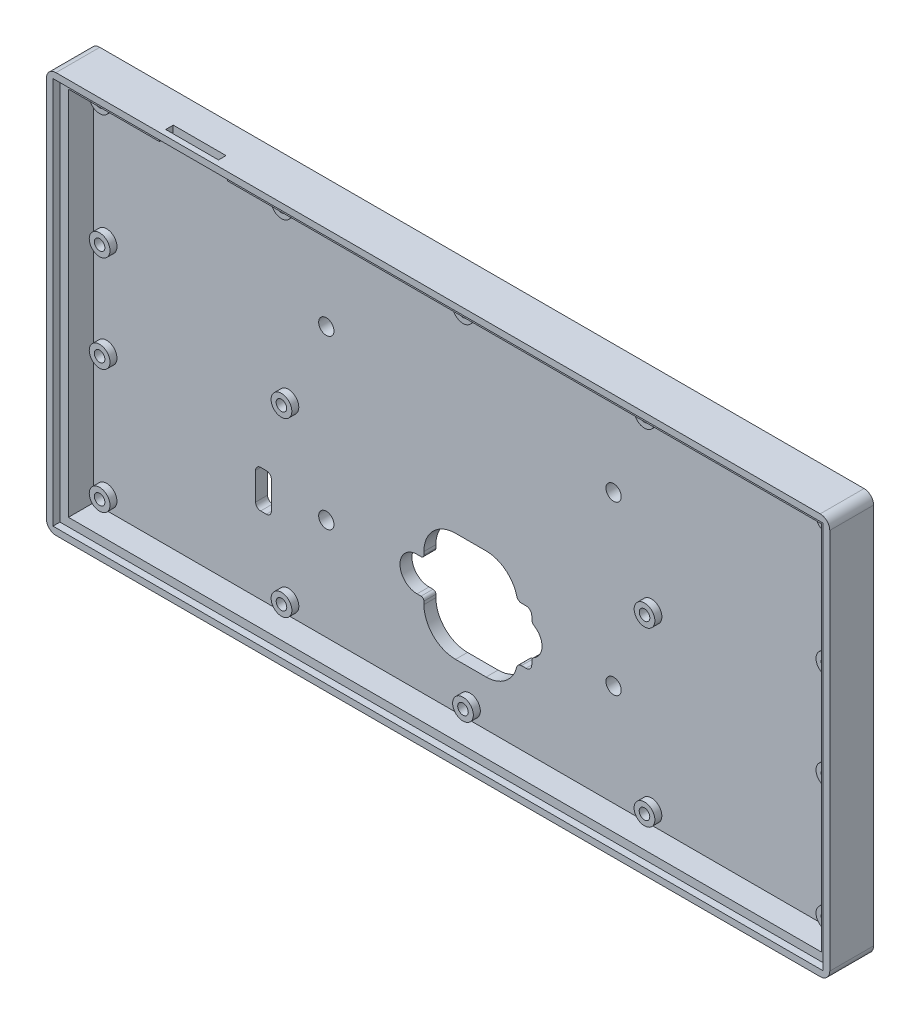
SolidWorks part; units mm, degrees
ref_plane "Front Plane" through (0, 0, 0) normal (0, 0, 1) x (1, 0, 0)
ref_plane "Top Plane" through (0, 0, 0) normal (0, 1, 0) x (1, 0, 0)
ref_plane "Right Plane" through (0, 0, 0) normal (1, 0, 0) x (0, 0, -1)
sketch "PCB" plane through (0, 0, 0) normal (0, 0, 1) x (1, 0, 0)
  line L0 (96.2635, 45.5524) -> (101.8921, 45.5524) construction
  line L1 (-101.8921, 51.181) -> (101.8921, 51.181) construction
  line L2 (-101.8921, 51.181) -> (-101.8921, -51.181) construction
  line L3 (-101.8921, -51.181) -> (101.8921, -51.181) construction
  line L4 (101.8921, 51.181) -> (101.8921, -51.181) construction
  line L5 (-101.8921, 51.181) -> (101.8921, -51.181) construction
  line L6 (-101.8921, -51.181) -> (101.8921, 51.181) construction
  line L7 (96.2635, 45.5524) -> (96.2635, 51.181) construction
  line L8 (-96.2635, 45.5524) -> (-101.8921, 45.5524) construction
  line L9 (-96.2635, -45.5524) -> (-96.2635, -51.181) construction
  line L10 (-92.8243, 0) -> (-92.8243, 25.6794) construction
  line L11 (-98.8568, 31.7119) -> (-86.7918, 31.7119)
  line L12 (-98.8568, 31.7119) -> (-98.8568, 19.6469)
  line L13 (-98.8568, 19.6469) -> (-86.7918, 19.6469)
  line L14 (-86.7918, 31.7119) -> (-86.7918, 19.6469)
  line L15 (-98.8568, 31.7119) -> (-86.7918, 19.6469) construction
  line L16 (-98.8568, 19.6469) -> (-86.7918, 31.7119) construction
  line L17 (-98.8568, 6.0325) -> (-86.7918, 6.0325)
  line L18 (-98.8568, 6.0325) -> (-98.8568, -6.0325)
  line L19 (-98.8568, -6.0325) -> (-86.7918, -6.0325)
  line L20 (-86.7918, 6.0325) -> (-86.7918, -6.0325)
  line L21 (-98.8568, 6.0325) -> (-86.7918, -6.0325) construction
  line L22 (-98.8568, -6.0325) -> (-86.7918, 6.0325) construction
  line L23 (-98.8568, -19.6469) -> (-86.7918, -19.6469)
  line L24 (-98.8568, -19.6469) -> (-98.8568, -31.7119)
  line L25 (-98.8568, -31.7119) -> (-86.7918, -31.7119)
  line L26 (-86.7918, -19.6469) -> (-86.7918, -31.7119)
  line L27 (-98.8568, -19.6469) -> (-86.7918, -31.7119) construction
  line L28 (-98.8568, -31.7119) -> (-86.7918, -19.6469) construction
  line L29 (86.7918, 31.7119) -> (98.8568, 31.7119)
  line L30 (86.7918, 31.7119) -> (86.7918, 19.6469)
  line L31 (86.7918, 19.6469) -> (98.8568, 19.6469)
  line L32 (98.8568, 31.7119) -> (98.8568, 19.6469)
  line L33 (86.7918, 31.7119) -> (98.8568, 19.6469) construction
  line L34 (86.7918, 19.6469) -> (98.8568, 31.7119) construction
  line L35 (86.7918, 6.0325) -> (98.8568, 6.0325)
  line L36 (86.7918, 6.0325) -> (86.7918, -6.0325)
  line L37 (86.7918, -6.0325) -> (98.8568, -6.0325)
  line L38 (98.8568, 6.0325) -> (98.8568, -6.0325)
  line L39 (86.7918, 6.0325) -> (98.8568, -6.0325) construction
  line L40 (86.7918, -6.0325) -> (98.8568, 6.0325) construction
  line L41 (86.7918, -19.6469) -> (98.8568, -19.6469)
  line L42 (86.7918, -19.6469) -> (86.7918, -31.7119)
  line L43 (86.7918, -31.7119) -> (98.8568, -31.7119)
  line L44 (98.8568, -19.6469) -> (98.8568, -31.7119)
  line L45 (86.7918, -19.6469) -> (98.8568, -31.7119) construction
  line L46 (86.7918, -31.7119) -> (98.8568, -19.6469) construction
  line L47 (-92.8243, 0) -> (-92.8243, -25.6794) construction
  line L48 (-92.8243, 25.6794) -> (-101.8921, 25.6794) construction
  line L49 (92.8243, 25.6794) -> (101.8921, 25.6794) construction
  line L50 (-3.114, -17.4711) -> (-3.114, -27.7327) construction
  circle A0 centre (-96.2635, 45.5524) radius 0.9995
  circle A1 centre (-96.2635, -45.5524) radius 0.9995
  circle A2 centre (96.2635, -45.5524) radius 0.9995
  circle A3 centre (96.2635, 45.5524) radius 0.9995
  circle A4 centre (-3.114, -17.4711) radius 1.9939
  circle A5 centre (-3.114, -27.7327) radius 1.9939
  point P0 (0, 0)
  point P14 (-92.8243, 25.6794)
  point P23 (-92.8243, 0)
  point P28 (-92.8243, -25.6794)
  point P33 (92.8243, 25.6794)
  point P38 (92.8243, 0)
  point P43 (92.8243, -25.6794)
  point P54 (0.1092, -22.6019)
  point P55 (-7.5006, -22.6019)
  point P60 (-3.114, -22.6019)
  dimension "D4" = 1.999
  dimension "D14" = 3.9878
  dimension "D1" = 203.7842
  dimension "D2" = 102.362
  dimension "D3" = 5.6286
  dimension "D5" = 25.5016
  dimension "D6" = 25.5016
  dimension "D7" = 9.0678
  dimension "D8" = 12.065
  dimension "D9" = 102.0013
  dimension "D10" = 28.5791
  dimension "D11" = 7.6098
  dimension "D12" = 5.1308
  dimension "D13" = 3.2233
sketch "DT_plug" plane through (0, 0, 0) normal (0, 0, 1) x (1, 0, 0)
  line L0 (29.2774, -40.0231) -> (29.2774, -5.0981) construction
  dimension "D1" = 34.925
sketch "display_screen" plane through (0, 0, 0) normal (0, 0, 1) x (1, 0, 0)
  line L1 (-80.3275, 46.3296) -> (83.7565, 46.3296) construction
  line L2 (-80.3275, 46.3296) -> (-80.3275, -50.9016) construction
  line L3 (-80.3275, -50.9016) -> (83.7565, -50.9016) construction
  line L4 (83.7565, 46.3296) -> (83.7565, -50.9016) construction
  line L5 (-78.2955, 44.2976) -> (78.2955, 44.2976) construction
  line L6 (-78.2955, 44.2976) -> (-78.2955, -44.2976) construction
  line L7 (-78.2955, -44.2976) -> (78.2955, -44.2976) construction
  line L8 (78.2955, 44.2976) -> (78.2955, -44.2976) construction
  point P8 (0, 44.2976)
  point P10 (-78.2955, 0)
  dimension "D1" = 164.084
  dimension "D2" = 97.2312
  dimension "D3" = 6.604
  dimension "D4" = 2.032
  dimension "D5" = 2.032
  dimension "D6" = 5.461
ref_plane "back_of_PCB" through (0, 0, -1.8542) normal (0, 0, 1) x (1, 0, 0)
ref_plane "back_PCB_clearance" through (0, 0, -8.4582) normal (0, 0, 1) x (1, 0, 0)
sketch "Sketch4" plane through (0, 0, 0) normal (0, 0, 1) x (1, 0, 0)
  line L0 (-102.1461, 51.4096) -> (-102.1461, 53.1596) construction
  line L1 (-102.1461, 51.4096) -> (102.1461, 51.4096)
  line L2 (-102.1461, 51.4096) -> (-102.1461, -51.4096)
  line L3 (-102.1461, -51.4096) -> (102.1461, -51.4096)
  line L4 (102.1461, 51.4096) -> (102.1461, -51.4096)
  line L5 (-103.8961, 53.1596) -> (103.8961, 53.1596)
  line L6 (-103.8961, 53.1596) -> (-103.8961, -53.1596)
  line L7 (-103.8961, -53.1596) -> (103.8961, -53.1596)
  line L8 (103.8961, 53.1596) -> (103.8961, -53.1596)
  line L9 (-102.1461, 51.4096) -> (-103.8961, 51.4096) construction
  line L10 (102.1461, -51.4096) -> (102.1461, -53.1596) construction
  line L11 (102.1461, -51.4096) -> (103.8961, -51.4096) construction
  line L12 (-101.8921, 51.181) -> (101.8921, 51.181) construction
  line L13 (-101.8921, 51.181) -> (-101.8921, -51.181) construction
  line L14 (101.8921, 51.181) -> (101.8921, -51.181) construction
  line L15 (-101.8921, -51.181) -> (101.8921, -51.181) construction
  dimension "D1" = 1.75
  dimension "D2" = 0.2286
  dimension "D3" = 0.254
  dimension "D4" = 0.254
  dimension "D5" = 0.2286
extrude "Boss-Extrude1" add sketch "Sketch4" against normal up to surface (1.8542 mm away) up to plane "back_of_PCB"
sketch "Sketch5" plane through (0, 0, -1.8542) normal (0, 0, -1) x (-1, 0, 0)
  line L1 (-103.8961, 53.1596) -> (103.8961, 53.1596)
  line L2 (-103.8961, 53.1596) -> (-103.8961, -53.1596)
  line L3 (-103.8961, -53.1596) -> (103.8961, -53.1596)
  line L4 (103.8961, 53.1596) -> (103.8961, -53.1596)
  line L6 (101.8921, 51.181) -> (-101.8921, 51.181) construction
  line L7 (-99.8931, 49.182) -> (99.8931, 49.182)
  line L8 (-99.8931, 49.182) -> (-99.8931, -49.182)
  line L9 (-99.8931, -49.182) -> (99.8931, -49.182)
  line L10 (99.8931, 49.182) -> (99.8931, -49.182)
  line L11 (-99.8931, 49.182) -> (-99.8931, 51.181) construction
  line L12 (-99.8931, 49.182) -> (-101.8921, 49.182) construction
  line L13 (-101.8921, 51.181) -> (-101.8921, -51.181) construction
  line L14 (99.8931, -49.182) -> (101.8921, -49.182) construction
  line L15 (101.8921, 51.181) -> (101.8921, -51.181) construction
  line L16 (99.8931, -49.182) -> (99.8931, -51.181) construction
  line L17 (101.8921, -51.181) -> (-101.8921, -51.181) construction
  dimension "D1" = 1.999
extrude "Boss-Extrude2" add sketch "Sketch5" along normal up to surface (6.604 mm away) up to plane "back_PCB_clearance"
sketch "Sketch6" plane through (0, 0, -8.4582) normal (0, 0, -1) x (-1, 0, 0)
  line L0 (11.7018, -27.8978) -> (11.7018, -28.6979) construction
  line L1 (-103.8961, 53.1596) -> (103.8961, 53.1596)
  line L2 (-103.8961, 53.1596) -> (-103.8961, -53.1596)
  line L3 (-103.8961, -53.1596) -> (103.8961, -53.1596)
  line L4 (103.8961, 53.1596) -> (103.8961, -53.1596)
  line L5 (3.8278, -8.6319) -> (-4.2865, -8.6319) construction
  line L6 (11.7018, -16.5059) -> (11.7018, -17.306) construction
  line L7 (3.8278, -36.5719) -> (-4.2865, -36.5719) construction
  line L11 (12.9718, -18.576) -> (14.0259, -18.576) construction
  line L13 (12.9718, -26.6278) -> (14.0259, -26.6278) construction
  line L15 (-13.6655, -15.9344) -> (-14.8666, -15.9344) construction
  line L16 (-15.8826, -27.4219) -> (-15.8826, -28.2534) construction
  line L17 (-13.6655, -29.2694) -> (-14.8666, -29.2694) construction
  line L18 (-15.8826, -16.9504) -> (-15.8826, -17.782) construction
  line L20 (12.2098, -27.8978) -> (12.2098, -28.6979)
  line L21 (3.8278, -37.0799) -> (-4.2865, -37.0799)
  line L22 (-13.6655, -29.7774) -> (-14.8666, -29.7774)
  line L23 (-16.3906, -27.4219) -> (-16.3906, -28.2534)
  line L24 (-16.3906, -16.9504) -> (-16.3906, -17.782)
  line L25 (-13.6655, -15.4264) -> (-14.8666, -15.4264)
  line L26 (3.8278, -8.1239) -> (-4.2865, -8.1239)
  line L27 (12.2098, -16.5059) -> (12.2098, -17.306)
  line L28 (12.9718, -18.068) -> (14.0259, -18.068)
  line L29 (12.9718, -27.1358) -> (14.0259, -27.1358)
  arc A0 (-16.7989, -19.407) -> (-16.7989, -25.7969) centre (-14.8666, -22.6019) ccw construction
  arc A1 (12.9718, -18.576) -> (11.7018, -17.306) centre (12.9718, -17.306) cw construction
  arc A2 (12.9718, -26.6278) -> (11.7018, -27.8978) centre (12.9718, -27.8978) ccw construction
  arc A3 (14.0259, -26.6278) -> (14.0259, -18.576) centre (14.0259, -22.6019) ccw construction
  arc A4 (11.7018, -28.6979) -> (3.8278, -36.5719) centre (3.8278, -28.6979) cw construction
  arc A5 (11.7018, -16.5059) -> (3.8278, -8.6319) centre (3.8278, -16.5059) ccw construction
  arc A6 (-4.2865, -8.6319) -> (-11.9202, -14.5755) centre (-4.2865, -16.5059) ccw construction
  arc A7 (-11.9202, -14.5755) -> (-13.6655, -15.9344) centre (-13.6655, -14.1342) cw construction
  arc A8 (-4.2865, -36.5719) -> (-11.9202, -30.6283) centre (-4.2865, -28.6979) cw construction
  arc A9 (-11.9202, -30.6283) -> (-13.6655, -29.2694) centre (-13.6655, -31.0697) ccw construction
  arc A10 (-14.8666, -15.9344) -> (-15.8826, -16.9504) centre (-14.8666, -16.9504) ccw construction
  arc A11 (-15.8826, -17.782) -> (-16.7989, -19.407) centre (-17.7817, -17.782) cw construction
  arc A12 (-15.8826, -27.4219) -> (-16.7989, -25.7969) centre (-17.7817, -27.4219) ccw construction
  arc A13 (-15.8826, -28.2534) -> (-14.8666, -29.2694) centre (-14.8666, -28.2534) ccw construction
  arc A14 (12.2098, -28.6979) -> (3.8278, -37.0799) centre (3.8278, -28.6979) cw
  arc A15 (-4.2865, -37.0799) -> (-12.4127, -30.7529) centre (-4.2865, -28.6979) cw
  arc A16 (-12.4127, -30.7529) -> (-13.6655, -29.7774) centre (-13.6655, -31.0697) ccw
  arc A17 (-16.3906, -28.2534) -> (-14.8666, -29.7774) centre (-14.8666, -28.2534) ccw
  arc A18 (-16.3906, -27.4219) -> (-17.0618, -26.2315) centre (-17.7817, -27.4219) ccw
  arc A19 (-17.0618, -18.9723) -> (-17.0618, -26.2315) centre (-14.8666, -22.6019) ccw
  arc A20 (-16.3906, -17.782) -> (-17.0618, -18.9723) centre (-17.7817, -17.782) cw
  arc A21 (-14.8666, -15.4264) -> (-16.3906, -16.9504) centre (-14.8666, -16.9504) ccw
  arc A22 (-12.4127, -14.451) -> (-13.6655, -15.4264) centre (-13.6655, -14.1342) cw
  arc A23 (-4.2865, -8.1239) -> (-12.4127, -14.451) centre (-4.2865, -16.5059) ccw
  arc A24 (12.2098, -16.5059) -> (3.8278, -8.1239) centre (3.8278, -16.5059) ccw
  arc A25 (12.9718, -18.068) -> (12.2098, -17.306) centre (12.9718, -17.306) cw
  arc A26 (14.0259, -27.1358) -> (14.0259, -18.068) centre (14.0259, -22.6019) ccw
  arc A27 (12.9718, -27.1358) -> (12.2098, -27.8978) centre (12.9718, -27.8978) ccw
  point P6 (-0.1092, -22.6019)
  dimension "D7" = 3.7338
  dimension "D9" = 1.27
  dimension "D3" = 1.0541
  dimension "D10" = 7.874
  dimension "D13" = 1.8002
  dimension "D16" = 1.016
  dimension "D17" = 1.8991
  dimension "D2" = 11.811
  dimension "D4" = 13.97
  dimension "D5" = 15.7734
  dimension "D6" = 6.6675
  dimension "D8" = 1.016
  dimension "D11" = 0.8001
  dimension "D12" = 13.97
  dimension "D14" = 8.1143
  dimension "D15" = 6.6675
  dimension "D22" = 0.508
extrude "Boss-Extrude3" add sketch "Sketch6" along normal blind 3.175
sketch "Sketch10" plane through (0, 0, -11.6332) normal (0, 0, -1) x (-1, 0, 0)
  line L0 (-38.1, 22.225) -> (38.1, 22.225) construction
  line L1 (38.1, 22.225) -> (38.1, -22.225) construction
  line L3 (38.1, 22.225) -> (38.1, 53.1596) construction
  line L4 (-103.8961, 53.1596) -> (103.8961, 53.1596) construction
  line L5 (38.1, -22.225) -> (38.1, -53.1596) construction
  line L6 (103.8961, -53.1596) -> (-103.8961, -53.1596) construction
  circle A0 centre (-38.1, 22.225) radius 2.032
  circle A1 centre (-38.1, 22.225) radius 5.207 construction
  circle A2 centre (-38.1, -22.225) radius 5.207 construction
  circle A3 centre (-38.1, -22.225) radius 2.032
  circle A4 centre (38.1, -22.225) radius 2.032
  circle A5 centre (38.1, -22.225) radius 5.207 construction
  circle A6 centre (38.1, 22.225) radius 2.032
  circle A7 centre (38.1, 22.225) radius 5.207 construction
  point P12 (0, 22.225)
  dimension "D1" = 4.064
  dimension "D2" = 3.175
  dimension "D3" = 76.2
  dimension "D4" = 44.45
extrude "Cut-Extrude1" cut sketch "Sketch10" against normal up to next
fillet "Fillet1" radius 2.54 4 edges at (103.8961, 53.1596, -5.8166) (103.8961, -53.1596, -5.8166) (-103.8961, -53.1596, -5.8166) (-103.8961, 53.1596, -5.8166)
sketch "Sketch11" plane through (0, 0, -8.4582) normal (0, 0, 1) x (1, 0, 0)
  line L0 (-96.3835, 45.671) -> (-96.3835, 51.4096) construction
  line L1 (-96.3835, 45.671) -> (96.3835, 45.671) construction
  line L2 (-96.3835, 45.671) -> (-96.3835, -45.671) construction
  line L3 (-96.3835, -45.671) -> (96.3835, -45.671) construction
  line L4 (96.3835, 45.671) -> (96.3835, -45.671) construction
  line L5 (-102.1461, 51.4096) -> (102.1461, 51.4096) construction
  line L6 (-96.3835, 45.671) -> (-102.1461, 45.671) construction
  line L7 (-102.1461, 51.4096) -> (-102.1461, -51.4096) construction
  line L8 (96.3835, -45.671) -> (102.1461, -45.671) construction
  line L9 (102.1461, -51.4096) -> (102.1461, 51.4096) construction
  line L10 (96.3835, -45.671) -> (96.3835, -51.4096) construction
  line L11 (102.1461, -51.4096) -> (-102.1461, -51.4096) construction
  circle A0 centre (-96.3835, 45.671) radius 1.4
  circle A1 centre (0, 45.671) radius 1.4
  circle A2 centre (96.3835, 45.671) radius 1.4
  circle A3 centre (-96.3835, -45.671) radius 1.4
  circle A4 centre (96.3835, -45.671) radius 1.4
  circle A5 centre (96.3835, -12.808) radius 1.4
  circle A6 centre (96.3835, 12.808) radius 1.4
  circle A7 centre (0, -45.671) radius 1.4
  circle A8 centre (-96.3835, -12.808) radius 1.4
  circle A9 centre (-96.3835, 12.808) radius 1.4
  circle A10 centre (-48.1435, 45.671) radius 1.4
  circle A11 centre (48.1435, 45.671) radius 1.4
  circle A12 centre (48.1435, -45.671) radius 1.4
  circle A13 centre (-48.1435, -45.671) radius 1.4
  circle A14 centre (-48.1545, 0.033) radius 1.4
  circle A15 centre (48.1545, 0.033) radius 1.4
  dimension "D3" = 2.8
  dimension "D1" = 91.342
  dimension "D2" = 192.767
  dimension "D4" = 48.24
  dimension "D5" = 48.24
  dimension "D6" = 32.863
  dimension "D7" = 32.863
  dimension "D8" = 48.229
  dimension "D9" = 45.638
  dimension "D10" = 48.229
  dimension "D11" = 45.638
extrude "Cut-Extrude2" cut sketch "Sketch11" against normal up to next
sketch "Sketch12" plane through (0, 53.1596, 0) normal (0, 1, 0) x (1, 0, 0)
  line L0 (101.3561, 0) -> (-101.3561, 0) construction
  line L1 (-73.7461, 3.5) -> (-59.7461, 3.5)
  line L2 (-73.7461, 3.5) -> (-73.7461, 1.5)
  line L3 (-73.7461, 1.5) -> (-59.7461, 1.5)
  line L4 (-59.7461, 3.5) -> (-59.7461, 1.5)
  line L6 (-103.8961, 0) -> (-103.8961, 11.6332) construction
  dimension "D1" = 1.5
  dimension "D2" = 14
  dimension "D3" = 30.15
  dimension "D4" = 2
extrude "Cut-Extrude3" cut sketch "Sketch12" against normal up to next
sketch "Sketch13" plane through (0, 0, -1.8542) normal (0, 0, 1) x (1, 0, 0)
  line L0 (-59.7461, 51.4096) -> (102.1461, 51.4096) construction
  line L1 (-75.7461, 49.182) -> (-57.7461, 49.182)
  line L2 (-75.7461, 49.182) -> (-75.7461, 51.4096)
  line L3 (-75.7461, 51.4096) -> (-57.7461, 51.4096)
  line L4 (-57.7461, 49.182) -> (-57.7461, 51.4096)
  line L5 (99.8931, 49.182) -> (-99.8931, 49.182) construction
  line L6 (-73.7461, 51.4096) -> (-73.7461, 49.182) construction
  line L7 (-59.7461, 49.182) -> (-59.7461, 53.1596) construction
  point P6 (-62.5878, 49.7704)
  point P7 (-76.0514, 49.182)
  dimension "D1" = 2
  dimension "D2" = 2
extrude "Cut-Extrude4" cut sketch "Sketch13" against normal up to surface (1.6458 mm away) up to face at (-66.7461, 51.1708, -3.5)
sketch "Sketch14" plane through (0, 0, -8.4582) normal (0, 0, 1) x (1, 0, 0)
  circle A0 centre (-96.3835, 45.671) radius 1.4
  circle A1 centre (-96.3835, 45.671) radius 2.75
  circle A3 centre (-96.3835, 45.671) radius 1.4 construction
  circle A4 centre (-48.1435, 45.671) radius 2.75
  circle A5 centre (-48.1435, 45.671) radius 1.4
  circle A6 centre (0, 45.671) radius 1.4
  circle A7 centre (0, 45.671) radius 2.75
  circle A8 centre (48.1435, 45.671) radius 1.4
  circle A9 centre (48.1435, 45.671) radius 2.75
  circle A10 centre (96.3835, 45.671) radius 1.4
  circle A11 centre (96.3835, 45.671) radius 2.75
  circle A12 centre (-96.3835, 12.808) radius 1.4
  circle A13 centre (-96.3835, 12.808) radius 2.75
  circle A14 centre (-48.1545, 0.033) radius 1.4
  circle A15 centre (-48.1545, 0.033) radius 2.75
  circle A16 centre (-96.3835, -12.808) radius 1.4
  circle A17 centre (-96.3835, -12.808) radius 2.75
  circle A18 centre (-96.3835, -45.671) radius 1.4
  circle A19 centre (-96.3835, -45.671) radius 2.75
  circle A20 centre (-48.1435, -45.671) radius 1.4
  circle A21 centre (-48.1435, -45.671) radius 2.75
  circle A22 centre (0, -45.671) radius 1.4
  circle A23 centre (0, -45.671) radius 2.75
  circle A24 centre (48.1545, 0.033) radius 1.4
  circle A25 centre (48.1545, 0.033) radius 2.75
  circle A26 centre (48.1435, -45.671) radius 1.4
  circle A27 centre (48.1435, -45.671) radius 2.75
  circle A28 centre (96.3835, -45.671) radius 1.4
  circle A29 centre (96.3835, -45.671) radius 2.75
  circle A30 centre (96.3835, -12.808) radius 1.4
  circle A31 centre (96.3835, -12.808) radius 2.75
  circle A32 centre (96.3835, 12.808) radius 1.4
  circle A33 centre (96.3835, 12.808) radius 2.75
  circle A34 centre (-48.1435, 45.671) radius 1.4 construction
  circle A35 centre (0, 45.671) radius 1.4 construction
  circle A36 centre (48.1435, 45.671) radius 1.4 construction
  circle A37 centre (96.3835, 45.671) radius 1.4 construction
  circle A38 centre (96.3835, 12.808) radius 1.4 construction
  circle A39 centre (48.1545, 0.033) radius 1.4 construction
  circle A40 centre (-48.1545, 0.033) radius 1.4 construction
  circle A41 centre (-96.3835, 12.808) radius 1.4 construction
  circle A42 centre (-96.3835, -12.808) radius 1.4 construction
  circle A43 centre (-96.3835, -45.671) radius 1.4 construction
  circle A44 centre (-48.1435, -45.671) radius 1.4 construction
  circle A45 centre (0, -45.671) radius 1.4 construction
  circle A46 centre (48.1435, -45.671) radius 1.4 construction
  circle A47 centre (96.3835, -45.671) radius 1.4 construction
  circle A48 centre (96.3835, -12.808) radius 1.4 construction
  point P97 (96.4877, 45.671)
  dimension "D1" = 5.5
extrude "Boss-Extrude4" add sketch "Sketch14" along normal blind 1.85
sketch "Sketch15" plane through (0, 0, -8.4582) normal (0, 0, 1) x (1, 0, 0)
  line L0 (-99.8931, 49.182) -> (-99.8931, -49.182) construction
  line L1 (-55.5121, -18.827) -> (-54.0121, -18.827)
  line L2 (-56.8621, -20.177) -> (-56.8621, -27.477)
  line L3 (-55.5121, -28.827) -> (-54.0121, -28.827)
  line L4 (-52.6621, -20.177) -> (-52.6621, -27.477)
  line L5 (-99.8931, -49.182) -> (99.8931, -49.182) construction
  arc A0 (-54.0121, -28.827) -> (-52.6621, -27.477) centre (-54.0121, -27.477) ccw
  arc A1 (-56.8621, -27.477) -> (-55.5121, -28.827) centre (-55.5121, -27.477) ccw
  arc A2 (-55.5121, -18.827) -> (-56.8621, -20.177) centre (-55.5121, -20.177) ccw
  arc A3 (-54.0121, -18.827) -> (-52.6621, -20.177) centre (-54.0121, -20.177) cw
  point P10 (-52.6621, -28.827)
  point P13 (-56.8621, -28.827)
  point P16 (-56.8621, -18.827)
  dimension "D5" = 1.35
  dimension "D1" = 43.031
  dimension "D2" = 4.2
  dimension "D3" = 10
  dimension "D4" = 20.355
extrude "Cut-Extrude5" cut sketch "Sketch15" against normal up to next
